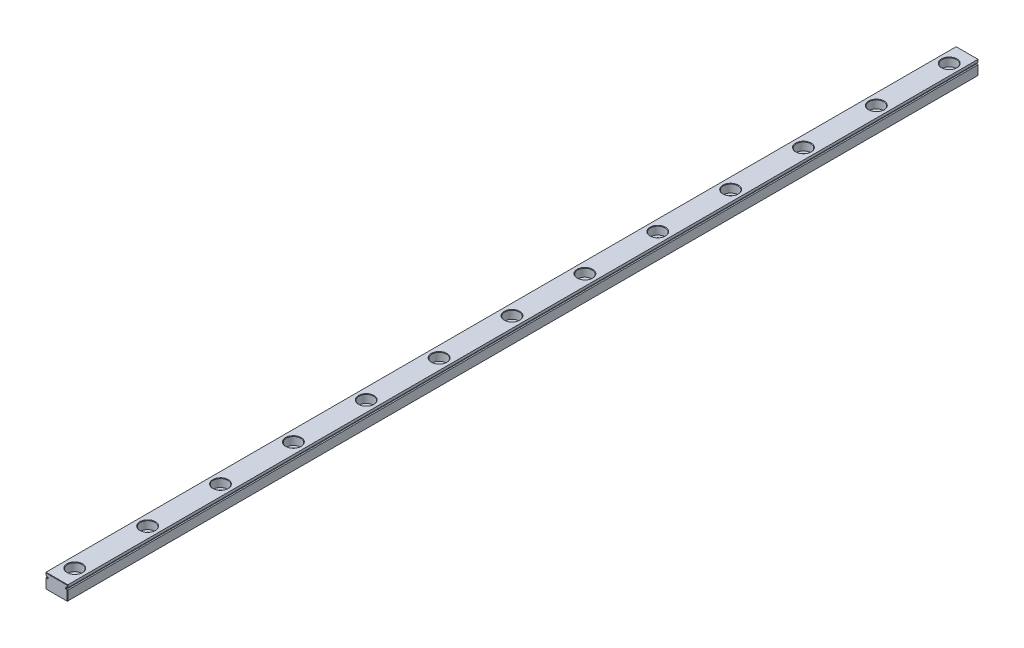
SolidWorks part; units mm, degrees
ref_plane "Front Plane" through (0, 0, 0) normal (0, 0, 1) x (1, 0, 0)
ref_plane "Top Plane" through (0, 0, 0) normal (0, 1, 0) x (1, 0, 0)
ref_plane "Right Plane" through (0, 0, 0) normal (1, 0, 0) x (0, 0, -1)
sketch "Sketch1" plane through (0, 0, 0) normal (0, 0, 1) x (1, 0, 0)
  line L0 (12.2152, 8.9783) -> (12.2152, 7.5373)
  line L1 (11.7152, 7.2283) -> (11.2152, 7.2283)
  line L2 (11.2152, 7.2283) -> (11.2152, 6.7283)
  line L3 (11.2152, 6.7283) -> (11.7152, 6.7283)
  line L4 (12.2152, 6.4192) -> (12.2152, 1.2783)
  line L5 (12.2152, 1.2783) -> (11.9152, 0.9783)
  line L6 (11.9152, 0.9783) -> (0.5152, 0.9783)
  line L7 (0.5152, 0.9783) -> (0.2152, 1.2783)
  line L8 (0.2152, 1.2783) -> (0.2152, 6.4192)
  line L9 (0.7152, 6.7283) -> (1.2152, 6.7283)
  line L10 (1.2152, 6.7283) -> (1.2152, 7.2283)
  line L11 (1.2152, 7.2283) -> (0.7152, 7.2283)
  line L12 (0.2152, 7.5373) -> (0.2152, 8.9783)
  line L13 (0.2152, 8.9783) -> (12.2152, 8.9783)
  arc A0 (12.2152, 7.5373) -> (11.7152, 7.2283) centre (12.2152, 6.9783) ccw
  arc A1 (11.7152, 6.7283) -> (12.2152, 6.4192) centre (12.2152, 6.9783) ccw
  arc A2 (0.2152, 6.4192) -> (0.7152, 6.7283) centre (0.2152, 6.9783) ccw
  arc A3 (0.7152, 7.2283) -> (0.2152, 7.5373) centre (0.2152, 6.9783) ccw
  dimension "D1" = 8
  dimension "D2" = 12
extrude "Boss-Extrude1" add sketch "Sketch1" against normal blind 500
chamfer "Chamfer1" distance 0.2 angle 45 36 edges at (0.2152, 8.2578, 0) (0.5091, 7.4538, 0) (0.9652, 7.2283, 0) (1.2152, 6.9783, 0) (0.9652, 6.7283, 0) (0.5091, 6.5027, 0) (0.2152, 3.8488, 0) (0.3652, 1.1283, 0) (6.2152, 0.9783, 0) (12.0652, 1.1283, 0) (12.2152, 3.8488, 0) (11.9213, 6.5027, 0) (11.4652, 6.7283, 0) (11.2152, 6.9783, 0) (11.4652, 7.2283, 0) (11.9213, 7.4538, 0) (12.2152, 8.2578, 0) (6.2152, 8.9783, 0) (11.9213, 6.5027, -500) (11.4652, 6.7283, -500) (11.2152, 6.9783, -500) (11.4652, 7.2283, -500) (11.9213, 7.4538, -500) (12.2152, 8.2578, -500) (12.2152, 3.8488, -500) (12.0652, 1.1283, -500) (6.2152, 0.9783, -500) (0.3652, 1.1283, -500) (0.2152, 3.8488, -500) (0.5091, 6.5027, -500) (0.9652, 6.7283, -500) (1.2152, 6.9783, -500) (0.9652, 7.2283, -500) (0.5091, 7.4538, -500) (0.2152, 8.2578, -500) (6.2152, 8.9783, -500)
hole_wizard "CBORE for M4 Hex Head Machine Screw1" positions "Sketch2" profile "Sketch3" counterbore size "M4" standard "ANSI Metric" end condition through all
sketch "Sketch2" plane through (0, 8.9783, 0) normal (0, 1, 0) x (1, 0, 0)
  line L0 (6.2152, 0) -> (6.2152, 500) construction
  line L1 (12.0152, 0) -> (0.4152, 0) construction
  line L2 (0.4152, 500) -> (12.0152, 500) construction
  point P0 (6.2152, 10)
  dimension "D1" = 10
sketch "Sketch3" plane through (6.2152, 8.9783, -10) normal (1, 0, 0) x (0, 0, 1)
  line L0 (0, 0) -> (0, 8)
  line L1 (0, 8) -> (2.25, 8)
  line L3 (2.25, 8) -> (2.25, 4.5)
  line L4 (4, 4.5) -> (2.25, 4.5)
  line L5 (4, 4.5) -> (4, 0.25)
  line L6 (4, 0.25) -> (4.25, 0)
  line L7 (4.25, 0) -> (0, 0)
  line L8 (-4, 0.25) -> (-4.25, 0) construction
  line L11 (0, -6.35) -> (0, 107.95) construction
  dimension "Thru Hole Dia." = 4.5
  dimension "Thru Hole Depth" = 8
  dimension "C'Bore Dia." = 8
  dimension "C'Bore Depth" = 4.5
  dimension "Near C'Sink Dia." = 8.5
  dimension "Near C'Sink Angle" = 90
pattern_linear "LPattern1" count 13 spacing 40 along (0, 0, -1) of "CBORE for M4 Hex Head Machine Screw1"
